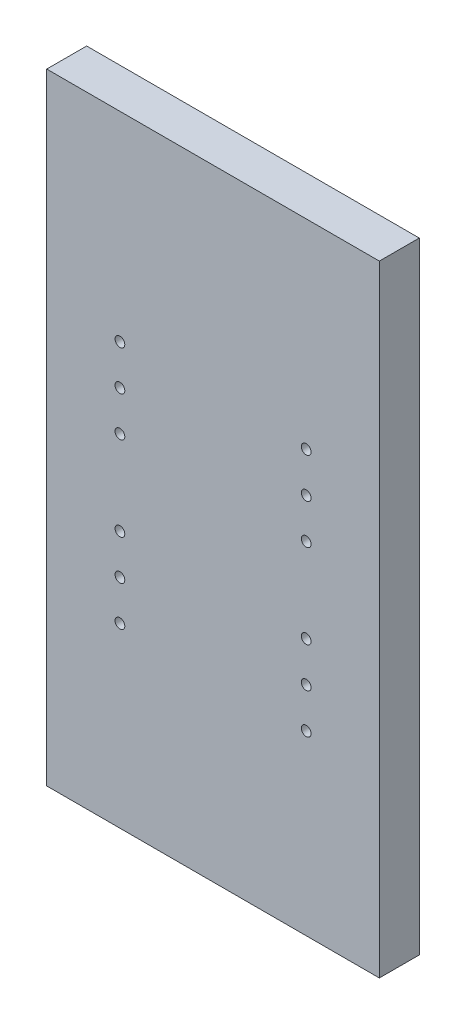
SolidWorks part; units mm, degrees
material "Maple"
ref_plane "Front Plane" through (0, 0, 0) normal (0, 0, 1) x (1, 0, 0)
ref_plane "Top Plane" through (0, 0, 0) normal (0, 1, 0) x (1, 0, 0)
ref_plane "Right Plane" through (0, 0, 0) normal (1, 0, 0) x (0, 0, -1)
sketch3d "3DSketch1"
  line L1 (296.0431, 1172.6929, 0) -> (146.0431, 1172.6929, 0)
  line L2 (296.0431, 1172.6929, 0) -> (296.0431, 892.6929, 0)
  line L3 (296.0431, 892.6929, 0) -> (146.0431, 892.6929, 0)
  line L4 (146.0431, 1172.6929, 0) -> (146.0431, 892.6929, 0)
  line L5 (296.0431, 1172.6929, 0) -> (146.0431, 892.6929, 0) construction
  line L6 (296.0431, 892.6929, 0) -> (146.0431, 1172.6929, 0) construction
  point P0 (221.0431, 1032.6929, 0)
  dimension "D1" = 280
  dimension "D2" = 150
extrude "Boss-Extrude1" add sketch "3DSketch1" along a picked direction on the side of the normal blind 18
sketch3d "3DSketch2"
  circle A0 centre (179.0431, 1082.6929, 20) radius 2.2 construction
  circle A1 centre (179.0431, 1082.6929, 20) radius 2.2
  circle A2 centre (179.0431, 1064.6929, 20) radius 2.2 construction
  circle A3 centre (179.0431, 1064.6929, 20) radius 2.2
  circle A4 centre (179.0431, 1046.6929, 20) radius 2.2 construction
  circle A5 centre (179.0431, 1046.6929, 20) radius 2.2
  circle A6 centre (179.0431, 1008.6929, 20) radius 2.2 construction
  circle A7 centre (179.0431, 1008.6929, 20) radius 2.2
  circle A8 centre (179.0431, 990.6929, 20) radius 2.2 construction
  circle A9 centre (179.0431, 990.6929, 20) radius 2.2
  circle A10 centre (179.0431, 972.6929, 20) radius 2.2 construction
  circle A11 centre (179.0431, 972.6929, 20) radius 2.2
  circle A12 centre (263.0431, 972.6929, 20) radius 2.2 construction
  circle A13 centre (263.0431, 972.6929, 20) radius 2.2
  circle A14 centre (263.0431, 990.6929, 20) radius 2.2 construction
  circle A15 centre (263.0431, 990.6929, 20) radius 2.2
  circle A16 centre (263.0431, 1008.6929, 20) radius 2.2 construction
  circle A17 centre (263.0431, 1008.6929, 20) radius 2.2
  circle A18 centre (263.0431, 1046.6929, 20) radius 2.2 construction
  circle A19 centre (263.0431, 1046.6929, 20) radius 2.2
  circle A20 centre (263.0431, 1082.6929, 20) radius 2.2 construction
  circle A21 centre (263.0431, 1082.6929, 20) radius 2.2
  circle A22 centre (263.0431, 1064.6929, 20) radius 2.2 construction
  circle A23 centre (263.0431, 1064.6929, 20) radius 2.2
  point P2 (179.0431, 1082.6929, 17.8)
  point P4 (179.0431, 1082.6929, 17.8)
  point P7 (179.0431, 1064.6929, 17.8)
  point P9 (179.0431, 1064.6929, 17.8)
  point P12 (179.0431, 1046.6929, 17.8)
  point P14 (179.0431, 1046.6929, 17.8)
  point P17 (179.0431, 1008.6929, 17.8)
  point P19 (179.0431, 1008.6929, 17.8)
  point P22 (179.0431, 990.6929, 17.8)
  point P24 (179.0431, 990.6929, 17.8)
  point P27 (179.0431, 972.6929, 17.8)
  point P29 (179.0431, 972.6929, 17.8)
  point P32 (263.0431, 972.6929, 17.8)
  point P34 (263.0431, 972.6929, 17.8)
  point P37 (263.0431, 990.6929, 17.8)
  point P39 (263.0431, 990.6929, 17.8)
  point P42 (263.0431, 1008.6929, 17.8)
  point P44 (263.0431, 1008.6929, 17.8)
  point P47 (263.0431, 1046.6929, 17.8)
  point P49 (263.0431, 1046.6929, 17.8)
  point P52 (263.0431, 1082.6929, 17.8)
  point P54 (263.0431, 1082.6929, 17.8)
  point P57 (263.0431, 1064.6929, 17.8)
  point P59 (263.0431, 1064.6929, 17.8)
  point P60 (0, 0, 0)
extrude "Cut-Extrude1" cut sketch "3DSketch2" along a picked direction on the side against the normal blind 18 contours A19 | A23 | A21 | A1 | A3 | A5 | A7 | A9 | A11 | A13 | A15 | A17
